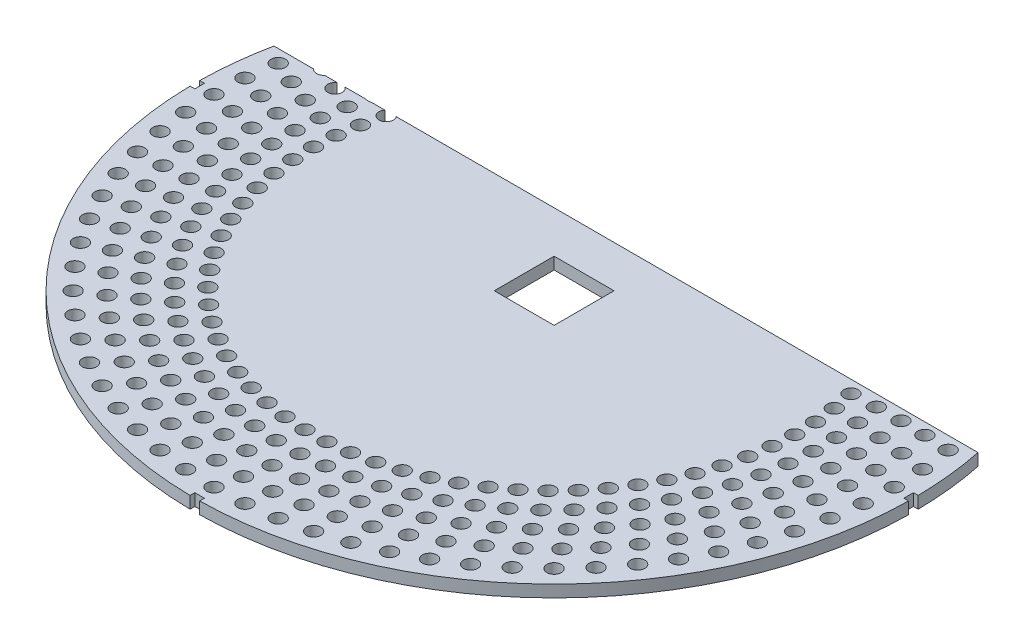
SolidWorks part; units mm, degrees
ref_plane "Front Plane" through (0, 0, 0) normal (0, 0, 1) x (1, 0, 0)
ref_plane "Top Plane" through (0, 0, 0) normal (0, 1, 0) x (1, 0, 0)
ref_plane "Right Plane" through (0, 0, 0) normal (1, 0, 0) x (0, 0, -1)
sketch "Sketch1" plane through (0, 0, 0) normal (0, 1, 0) x (1, 0, 0)
  line L1 (-12.5, -12.5) -> (12.5, -12.5)
  line L2 (-12.5, -12.5) -> (-12.5, 12.5)
  line L3 (-12.5, 12.5) -> (12.5, 12.5)
  line L4 (12.5, -12.5) -> (12.5, 12.5)
  line L5 (-12.5, -12.5) -> (12.5, 12.5) construction
  line L6 (-12.5, 12.5) -> (12.5, -12.5) construction
  circle A0 centre (0, 0) radius 150
  dimension "D1" = 25
  dimension "D2" = 25
  dimension "Tamanho" = 300
extrude "Boss-Extrude1" add sketch "Sketch1" along normal blind 5
sketch "Sketch4" plane through (0, 5, 0) normal (0, 1, 0) x (1, 0, 0)
  line L0 (-142, 0) -> (0, 0) construction
  line L1 (0, 0) -> (-132, -2.3041) construction
  line L2 (0, 0) -> (-122, -4.2603) construction
  line L3 (0, 0) -> (-112, -5.8697) construction
  line L4 (-102, -7.1325) -> (0, 0) construction
  circle A0 centre (-142, 0) radius 3
  circle A1 centre (-132, -2.3041) radius 3
  circle A2 centre (-122, -4.2603) radius 3
  circle A3 centre (-112, -5.8697) radius 3
  circle A4 centre (-102, -7.1325) radius 3
  dimension "D1" = 6
  dimension "D2" = 6
  dimension "D3" = 6
  dimension "D4" = 6
  dimension "D11" = 6
  dimension "Offset" = 1
  dimension "D5" = 1
  dimension "D6" = 1
  dimension "D7" = 142
  dimension "D8" = 10
  dimension "D9" = 10
  dimension "D10" = 10
  dimension "D12" = 1
  dimension "D13" = 10
extrude "Cut-Extrude3" cut sketch "Sketch4" against normal blind 10
pattern_circular "CirPattern3" count 72 over 360 about axis through (0, 5, 0) along (0, 1, 0) of "Cut-Extrude3"
sketch "Sketch9" plane through (0, 5, 0) normal (0, 1, 0) x (1, 0, 0)
  line L0 (0, -166.0677) -> (0, 166.0677)
  line L1 (225, 0) -> (-225, 0)
  point P6 (0, 0)
  point P10 (0, 0)
sketch "Sketch10" plane through (0, 5, 0) normal (0, 1, 0) x (1, 0, 0)
  line L0 (0, 0) -> (0, -190.7753) construction
  line L1 (-2, -148) -> (2, -148)
  line L2 (-2, -148) -> (-2, -152)
  line L3 (-2, -152) -> (2, -152)
  line L4 (2, -148) -> (2, -152)
  line L6 (0, -148) -> (0, -152) construction
  point P10 (0, -148)
  dimension "D1" = 4
  dimension "D2" = 4
  dimension "D3" = 148
extrude "Cut-Extrude4" cut sketch "Sketch10" against normal blind 5
pattern_circular "CirPattern4" count 4 over 360 about axis through (0, 5, 0) along (0, 1, 0) of "Cut-Extrude4"
sketch "Sketch11" plane through (0, 0, 0) normal (0, 0, 1) x (1, 0, 0)
  line L5 (-150, -10) -> (150, -10)
  line L6 (-150, -10) -> (-150, 10)
  line L7 (-150, 10) -> (150, 10)
  line L8 (150, -10) -> (150, 10)
  line L9 (-150, -10) -> (150, 10) construction
  line L10 (-150, 10) -> (150, -10) construction
  point P0 (0, 0)
  dimension "D1" = 20
  dimension "D2" = 300
extrude "Cut-Extrude5" cut sketch "Sketch11" against normal blind 150 from offset 30 offset against normal yes
equation "\"Tamanho\"=300"
equation "\"D5@Sketch4\"=\"Offset@Sketch4\""
equation "\"D6@Sketch4\"=\"Offset@Sketch4\""
equation "\"D12@Sketch4\"=\"Offset@Sketch4\""
equation "\"D2@Sketch4\"=\"D1@Sketch4\""
equation "\"D3@Sketch4\"=\"D1@Sketch4\""
equation "\"D4@Sketch4\"=\"D1@Sketch4\""
equation "\"D11@Sketch4\"=\"D1@Sketch4\""
